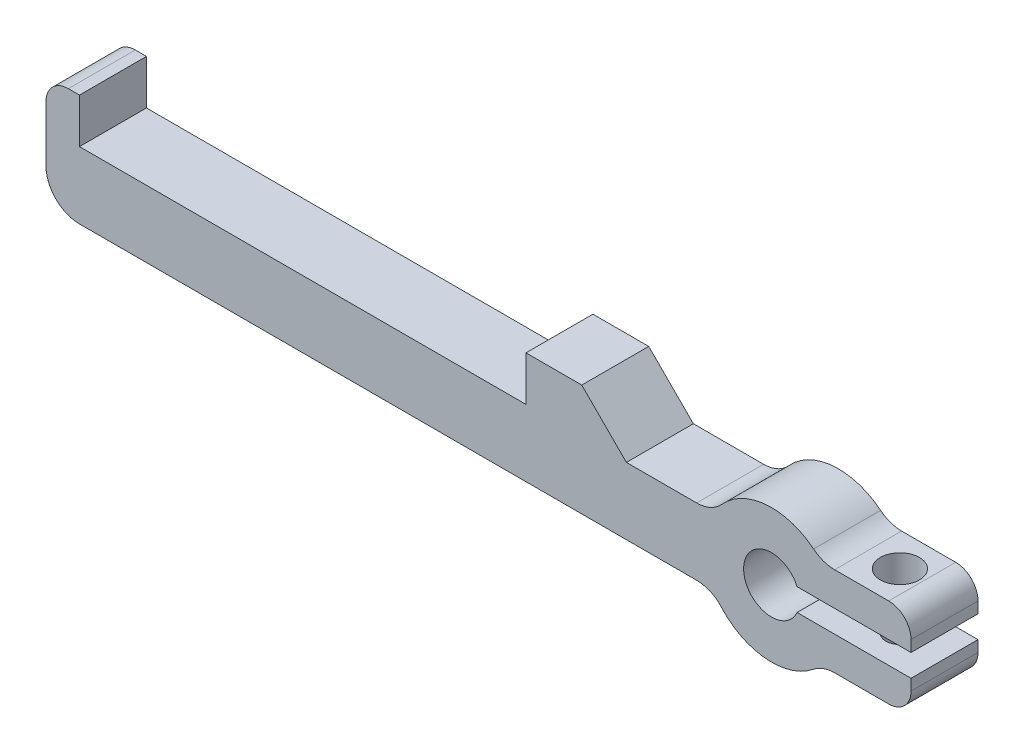
SolidWorks part; units mm, degrees
ref_plane "Front" through (0, 0, 0) normal (0, 0, 1) x (1, 0, 0)
ref_plane "Top" through (0, 0, 0) normal (0, 1, 0) x (1, 0, 0)
ref_plane "Right" through (0, 0, 0) normal (1, 0, 0) x (0, 0, -1)
sketch "Esquisse1" plane through (0, 0, 0) normal (0, 0, 1) x (1, 0, 0)
  circle A0 centre (0, 0) radius 6
  circle A1 centre (0, 0) radius 2.5
  dimension "D1" = 12
  dimension "D2" = 5
extrude "Boss.-Extru.1" add sketch "Esquisse1" along normal blind 6
sketch "Esquisse2" plane through (0, 0, 6) normal (0, 0, 1) x (1, 0, 0)
  line L0 (-3, 0) -> (0, 0) construction
  line L1 (-65, 3) -> (-3, 3)
  line L2 (-65, 3) -> (-65, -3)
  line L3 (-65, -3) -> (-3, -3)
  line L4 (-3, 3) -> (-3, -3)
  dimension "D1" = 6
  dimension "D2" = 3
  dimension "D3" = 62
extrude "Boss.-Extru.2" add sketch "Esquisse2" against normal up to surface (6 mm away) up to face at (6, 0, 0)
sketch "Esquisse3" plane through (0, 0, 6) normal (0, 0, 1) x (1, 0, 0)
  line L0 (2.5, 0) -> (0, 0) construction
  line L1 (2.5, 4) -> (12.5, 4)
  line L2 (2.5, 4) -> (2.5, -4)
  line L3 (2.5, -4) -> (12.5, -4)
  line L4 (12.5, 4) -> (12.5, -4)
  dimension "D1" = 8
  dimension "D2" = 2.5
  dimension "D3" = 10
extrude "Boss.-Extru.3" add sketch "Esquisse3" against normal up to surface (6 mm away) up to face at (-32.299, 0, 0)
fillet "Congé1" radius 3 5 edges at (-5.1962, 3, 3) (-5.1962, -3, 3) (-65, -3, 3) (4.4721, -4, 3) (4.4721, 4, 3)
sketch "Esquisse4" plane through (0, 0, 6) normal (0, 0, 1) x (1, 0, 0)
  line L0 (0.5, 0) -> (0, 0) construction
  line L1 (12.5, -1) -> (0.5, -1)
  line L2 (12.5, -1) -> (12.5, 1)
  line L3 (12.5, 1) -> (0.5, 1)
  line L4 (0.5, -1) -> (0.5, 1)
  line L5 (12.5, -4) -> (12.5, 4) construction
  dimension "D1" = 2
  dimension "D2" = 0.5
extrude "Enlèv. mat.-Extru.1" cut sketch "Esquisse4" against normal through all both and the other way through all
sketch "Esquisse5" plane through (0, 4, 0) normal (0, 1, 0) x (1, 0, 0)
  line L0 (12.5, -3) -> (8.5, -3) construction
  line L1 (12.5, 0) -> (12.5, -6) construction
  circle A0 centre (8.5, -3) radius 1.25
  dimension "D1" = 2.5
  dimension "D2" = 4
extrude "Enlèv. mat.-Extru.2" cut sketch "Esquisse5" against normal through all both and the other way through all
sketch "Esquisse6" plane through (0, 4, 0) normal (0, 1, 0) x (1, 0, 0)
  circle A0 centre (8.5, -3) radius 1.75
  dimension "D1" = 3.5
extrude "Enlèv. mat.-Extru.3" cut sketch "Esquisse6" against normal up to vertex (3 mm away) up to point (12.5, 1, 6)
fillet "Congé2" radius 2 2 edges at (12.5, -4, 3) (12.5, 4, 3)
sketch "Esquisse7" plane through (0, 0, 6) normal (0, 0, 1) x (1, 0, 0)
  line L0 (-6.7082, 3) -> (-65, 3) construction
  line L1 (-65, 3) -> (-62, 3)
  line L2 (-65, 3) -> (-65, 7)
  line L3 (-65, 7) -> (-62, 7)
  line L4 (-62, 3) -> (-62, 7)
  line L5 (-19, 3) -> (-22, 3)
  line L6 (-19, 3) -> (-19, 7)
  line L7 (-19, 7) -> (-22, 7)
  line L8 (-22, 3) -> (-22, 7)
  point P11 (-22, 5)
  dimension "D1" = 40
  dimension "D2" = 3
  dimension "D3" = 4
extrude "Boss.-Extru.4" add sketch "Esquisse7" against normal up to vertex (6 mm away) up to point (-6.7082, 3, 0)
chamfer "Chanfrein1" distance 6 angle 45 1 edges at (-19, 3, 3)
fillet "Congé3" radius 2 1 edges at (-65, 7, 3)
